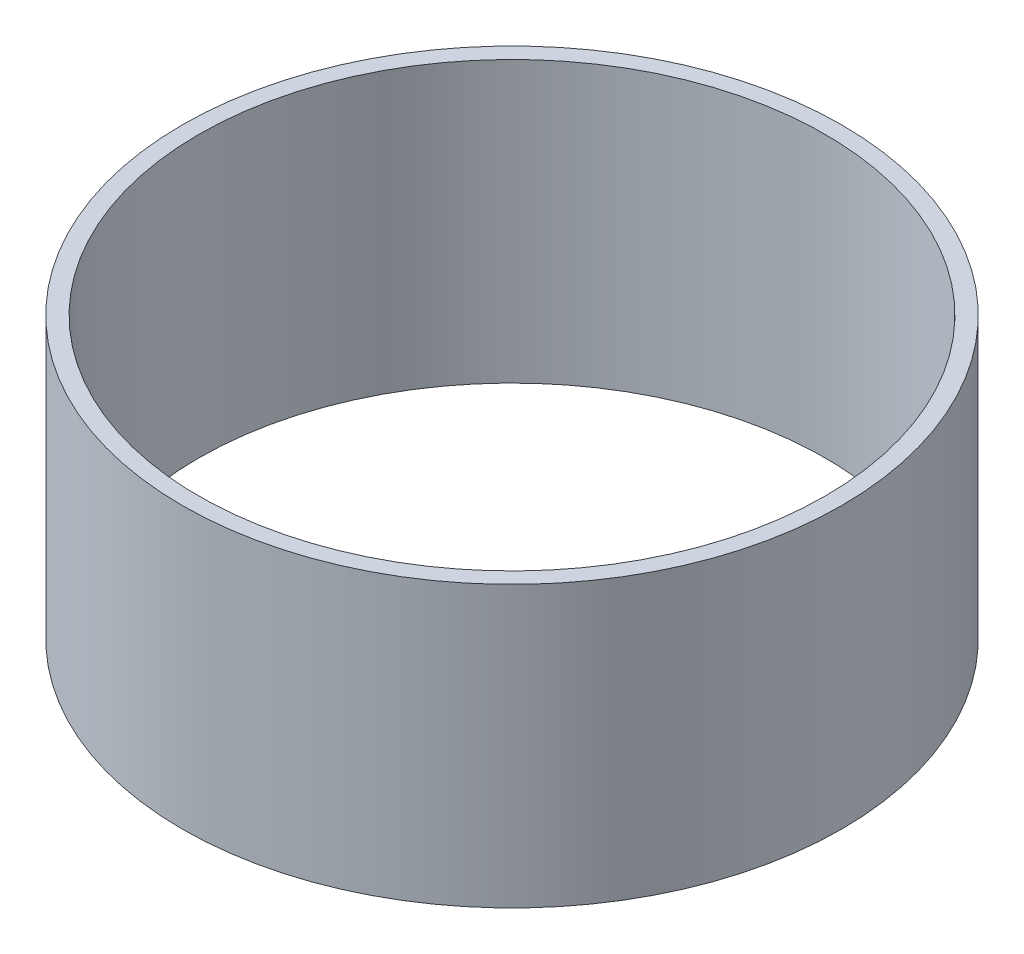
SolidWorks part; units mm, degrees
ref_plane "Front Plane" through (0, 0, 0) normal (0, 0, 1) x (1, 0, 0)
ref_plane "Top Plane" through (0, 0, 0) normal (0, 1, 0) x (1, 0, 0)
ref_plane "Right Plane" through (0, 0, 0) normal (1, 0, 0) x (0, 0, -1)
sketch "Sketch1" plane through (0, 0, 0) normal (0, 1, 0) x (1, 0, 0)
  circle A0 centre (0, 0) radius 60
  dimension "D1" = 120
extrude "Extrude-Thin1" add sketch "Sketch1" along normal blind 51 thin thin type one direction reverse wall 3
